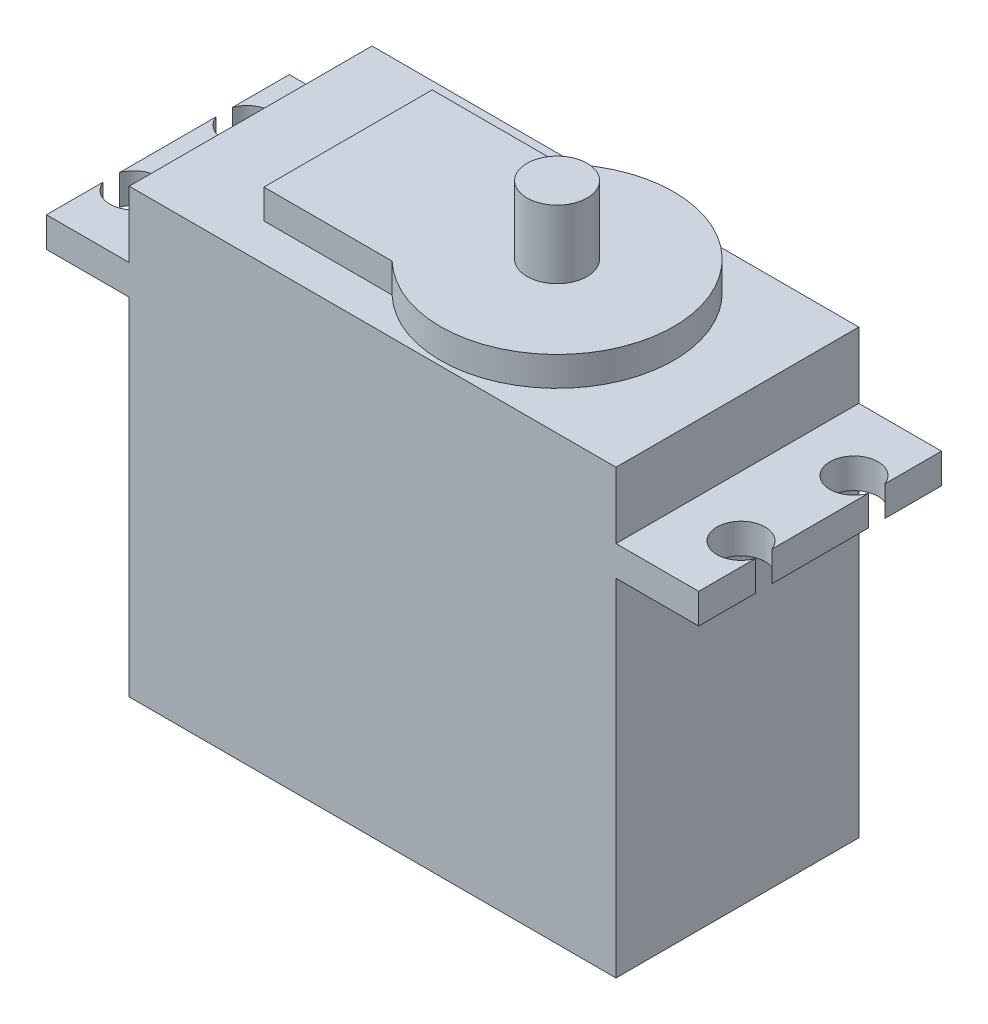
SolidWorks part; units mm, degrees
ref_plane "Alzado" through (0, 0, 0) normal (0, 0, 1) x (1, 0, 0)
ref_plane "Planta" through (0, 0, 0) normal (0, 1, 0) x (1, 0, 0)
ref_plane "Vista lateral" through (0, 0, 0) normal (1, 0, 0) x (0, 0, -1)
sketch "Croquis1" plane through (0, 0, 0) normal (0, 1, 0) x (1, 0, 0)
  line L1 (0, 0) -> (40.5, 0)
  line L2 (0, 0) -> (0, 20.2)
  line L3 (0, 20.2) -> (40.5, 20.2)
  line L4 (40.5, 0) -> (40.5, 20.2)
  dimension "D1" = 40.5
  dimension "D2" = 20.2
extrude "Saliente-Extruir1" add sketch "Croquis1" along normal blind 36.8
sketch "Croquis2" plane through (0, 36.8, 0) normal (0, 1, 0) x (1, 0, 0)
  line L1 (40.5, 0) -> (40.5, 20.2) construction
  line L2 (40.5, 10.1) -> (0, 10.1) construction
  line L3 (0, 20.2) -> (0, 0) construction
  line L9 (0, 17.1) -> (40.5, 17.1) construction
  line L10 (0, 3.1) -> (40.5, 3.1) construction
  line L12 (8.1065, 17.1) -> (8.1065, 3.1)
  line L13 (8.1065, 3.1) -> (18.7702, 3.1)
  line L14 (8.1065, 17.1) -> (18.7702, 17.1)
  circle A1 centre (25.5, 10.1) radius 9.7103
  dimension "D1" = 15
  dimension "D2" = 7
  dimension "D3" = 7
extrude "Saliente-Extruir2" add sketch "Croquis2" along normal blind 2.44 contours A1 | A1 L14 L12 L13 region at (12.4529, 36.8, -10.1) region at (25.5, 36.8, -10.1)
sketch "Croquis3" plane through (0, 39.24, 0) normal (0, 1, 0) x (1, 0, 0)
  circle A0 centre (25.5, 10.1) radius 2.5
  dimension "D1" = 5
extrude "Saliente-Extruir3" add sketch "Croquis3" along normal blind 5.66
sketch "Croquis4" plane through (0, 0, 0) normal (-1, 0, 0) x (0, 0, 1)
  line L0 (-20.2, 36.8) -> (-20.2, 0) construction
  line L1 (-20.2, 31.3) -> (0, 31.3)
  line L2 (-20.2, 31.3) -> (-20.2, 28.8)
  line L3 (-20.2, 28.8) -> (0, 28.8)
  line L4 (0, 31.3) -> (0, 28.8)
  line L5 (0, 36.8) -> (0, 0) construction
  line L8 (-20.2, 36.8) -> (0, 36.8) construction
  line L9 (-20.2, 0) -> (0, 0) construction
  dimension "D1" = 8
  dimension "D2" = 2.5
  dimension "D3" = 28.8
extrude "Saliente-Extruir4" add sketch "Croquis4" along normal blind 6.88
sketch "Croquis5" plane through (40.5, 0, 0) normal (1, 0, 0) x (0, 0, -1)
  line L0 (0, 36.8) -> (0, 0) construction
  line L1 (0, 31.3) -> (20.2, 31.3)
  line L2 (0, 31.3) -> (0, 28.8)
  line L3 (0, 28.8) -> (20.2, 28.8)
  line L4 (20.2, 31.3) -> (20.2, 28.8)
  line L5 (20.2, 36.8) -> (20.2, 0) construction
  line L9 (0, 0) -> (20.2, 0) construction
  dimension "D1" = 2.5
  dimension "D2" = 28.8
extrude "Saliente-Extruir5" add sketch "Croquis5" along normal blind 6.88
sketch "Croquis6" plane through (0, 31.3, 0) normal (0, 1, 0) x (1, 0, 0)
  line L0 (0, 20.2) -> (0, 0) construction
  line L1 (-6.88, 20.2) -> (-6.88, 0)
  line L2 (40.5, 20.2) -> (40.5, 0) construction
  line L3 (-6.88, 10.1) -> (47.38, 10.1) construction
  line L4 (47.38, 20.2) -> (47.38, 0) construction
  line L5 (47.38, 20.2) -> (47.38, 0)
  arc A0 (-6.88, 14.1177) -> (-6.88, 15.4823) centre (-5, 14.8) ccw
  arc A1 (-6.88, 4.7177) -> (-6.88, 6.0823) centre (-5, 5.4) ccw
  arc A2 (47.38, 15.4823) -> (47.38, 14.1177) centre (45.5, 14.8) ccw
  arc A3 (47.38, 6.0823) -> (47.38, 4.7177) centre (45.5, 5.4) ccw
  dimension "D1" = 4
  dimension "D2" = 4
  dimension "D5" = 4
  dimension "D6" = 4
  dimension "D3" = 5
  dimension "D4" = 5
  dimension "D7" = 5
  dimension "D8" = 5
  dimension "D9" = 4.7
  dimension "D10" = 4.7
  dimension "D11" = 4.7
  dimension "D12" = 4.7
extrude "Cortar-Extruir1" cut sketch "Croquis6" against normal through all contours L1 A1 | L1 A0 | L5 A2 | L5 A3 region at (-4.983, 31.3, -14.8) region at (-4.983, 31.3, -5.4) region at (45.483, 31.3, -5.4) region at (45.483, 31.3, -14.8)
